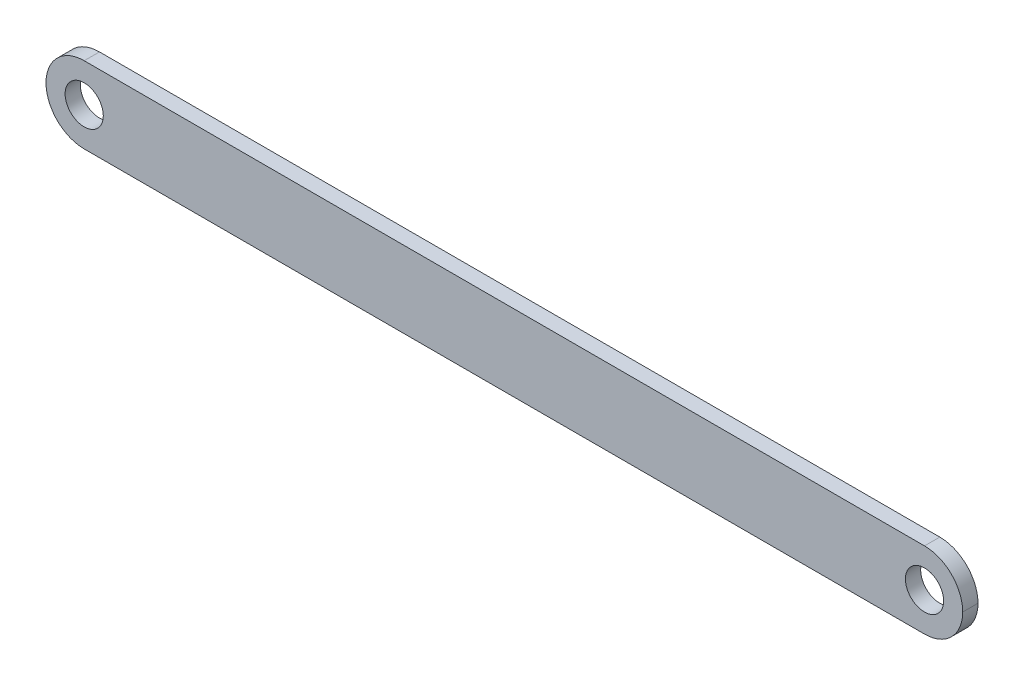
SolidWorks part; units mm, degrees
material "AISI 1020"
ref_plane "Front Plane" through (0, 0, 0) normal (0, 0, 1) x (1, 0, 0)
ref_plane "Top Plane" through (0, 0, 0) normal (0, 1, 0) x (1, 0, 0)
ref_plane "Right Plane" through (0, 0, 0) normal (1, 0, 0) x (0, 0, -1)
sketch "Sketch1" plane through (0, 0, 0) normal (0, 0, 1) x (1, 0, 0)
  line L1 (0, 0) -> (152.4, 0)
  line L2 (0, 0) -> (0, 12.7)
  line L3 (0, 12.7) -> (152.4, 12.7)
  line L4 (152.4, 0) -> (152.4, 12.7)
  circle A0 centre (6.35, 6.35) radius 3.175
  circle A1 centre (146.05, 6.35) radius 3.175
  point P9 (0, 6.35)
  point P10 (152.4, 6.35)
  dimension "D3" = 6.35
  dimension "D1" = 152.4
  dimension "D2" = 12.7
  dimension "D4" = 6.35
  dimension "D5" = 6.35
extrude "Boss-Extrude1" add sketch "Sketch1" along normal blind 2.54
fillet "Fillet2" radius 6.35 2 edges at (0, 0, 1.27) (0, 12.7, 1.27)
fillet "Fillet3" radius 6.35 2 edges at (152.4, 0, 1.27) (152.4, 12.7, 1.27)
